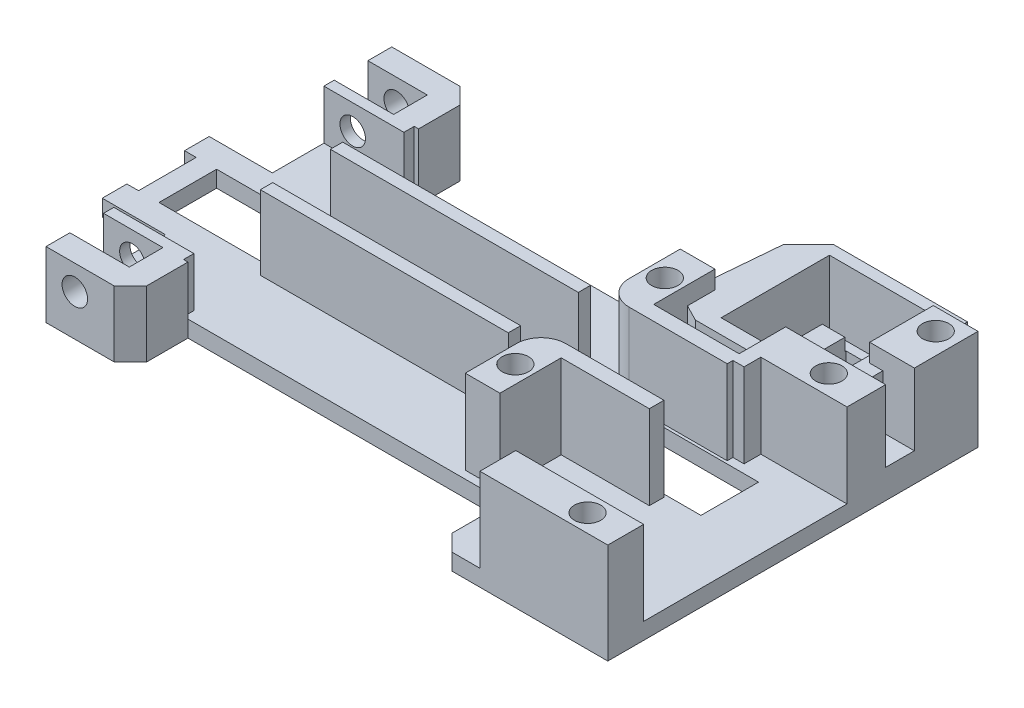
SolidWorks part; units mm, degrees
material "ABS"
ref_plane "前视基准面" through (0, 0, 0) normal (0, 0, 1) x (1, 0, 0)
ref_plane "上视基准面" through (0, 0, 0) normal (0, 1, 0) x (1, 0, 0)
ref_plane "右视基准面" through (0, 0, 0) normal (1, 0, 0) x (0, 0, -1)
sketch "草图1" plane through (0, 0, 0) normal (0, 1, 0) x (1, 0, 0)
  line L0 (-26.5, 14) -> (21.7831, 14)
  line L1 (44.6878, 18.1) -> (44.6878, 3.5) construction
  line L2 (44.6878, 14) -> (44.6878, -14)
  line L3 (44.6878, -18.1) -> (44.6878, -3.5) construction
  line L4 (-26.5, -14) -> (-26.5, -6.4892)
  line L5 (21.7831, -14) -> (-26.5, -14)
  line L6 (23.7831, -16) -> (23.7831, -20.4724)
  line L7 (25.7831, -22.4724) -> (44.6878, -22.4724)
  line L8 (44.6878, -18.1) -> (44.6878, -27.09) construction
  line L9 (49.6864, 0) -> (119.3782, 0) construction
  line L10 (39.6706, 22.4724) -> (44.6878, 22.4724)
  line L11 (23.7831, 16) -> (23.7831, 20.4724)
  line L12 (44.6878, 22.4724) -> (44.6878, 14)
  line L13 (44.6878, -14) -> (44.6878, -22.4724)
  line L14 (37.7008, 24.1809) -> (39.6706, 24.1809)
  line L15 (21.7831, 14) -> (23.7831, 16)
  line L16 (21.7831, -14) -> (23.7831, -16)
  line L17 (23.7831, -20.4724) -> (25.7831, -22.4724)
  line L18 (-32.6682, -6.4892) -> (-26.5, -6.4892)
  line L19 (23.7831, 20.4724) -> (23.7831, 21.4918)
  line L20 (-26.5, -21) -> (-36.5, 21) construction
  line L21 (-32.6682, 4.9064) -> (-32.6682, -4.9064)
  line L22 (-26.5, 21) -> (-36.5, -21) construction
  line L24 (-26.5, 6.4892) -> (-26.5, 14)
  line L25 (23.7831, 21.4918) -> (25.7831, 24.1809)
  line L26 (-32.6682, 3.5) -> (-31.2539, 3.5)
  line L27 (-32.6682, 3.5) -> (-32.6682, -3.5)
  line L28 (-32.6682, -3.5) -> (-31.2539, -3.5)
  line L29 (37.0236, 3.5) -> (37.0236, -3.5)
  line L30 (25.7831, 24.1809) -> (37.7008, 24.1809)
  line L31 (-31.2539, 3.5) -> (-31.2539, -3.5)
  line L32 (39.6706, 24.1809) -> (39.6706, 22.4724)
  line L33 (-32.6682, 4.9064) -> (-32.6682, 6.4892)
  line L34 (-28.7731, -3.5) -> (-28.7731, 3.5)
  line L35 (-32.6682, -4.9064) -> (-32.6682, -6.4892)
  line L36 (-28.7731, 3.5) -> (37.0236, 3.5)
  line L37 (-28.7731, -3.5) -> (37.0236, -3.5)
  line L38 (-32.6682, 6.4892) -> (-26.5, 6.4892)
  point P0 (0, 0)
  point P2 (23.7831, -14)
  point P6 (0, 0)
  point P12 (23.7831, -22.4724)
  point P18 (23.7831, 22.4724)
  point P20 (23.7831, 14)
  dimension "D1" = 7
  dimension "D2" = 28
  dimension "D4" = 2
extrude "凸台-拉伸1" add sketch "草图1" along normal blind 1 contours L4 L0 region at (-2.3584, 0, -13.0966)
extrude "凸台-拉伸4" add sketch "草图1<3>" against normal blind 1 contours L4 L0 region at (-2.3584, 0, -13.0966)
sketch "草图1<3>" plane through (0, 0, 0) normal (0, 1, 0) x (1, 0, 0) same geometry as "草图1"
sketch "草图2" plane through (0, 1, 0) normal (0, 1, 0) x (1, 0, 0)
  line L0 (25.7831, -22.4724) -> (44.6878, -22.4724) construction
  line L1 (29.1607, -22.4724) -> (44.6878, -22.4724)
  line L2 (29.1607, -22.4724) -> (29.1607, -18.118)
  line L3 (29.1607, -18.118) -> (44.6878, -18.118)
  line L4 (44.6878, -22.4724) -> (44.6878, -18.118)
  line L5 (44.6878, 6.5706) -> (34.2253, 6.5706)
  line L6 (44.6878, 22.4724) -> (44.6878, -22.4724) construction
  line L7 (34.2253, 6.5706) -> (34.2253, 4.5345)
  line L8 (34.2253, 4.5345) -> (32.5478, 4.5345)
  line L9 (32.5478, 4.5345) -> (32.5478, 11.2659)
  line L10 (32.5478, 11.2659) -> (44.6878, 11.2659)
  line L11 (22.1731, -9.0716) -> (22.1731, -5.6153)
  line L13 (17.9615, -9.0716) -> (17.9615, -13.0505)
  line L14 (17.9615, -13.0505) -> (22.1731, -13.0505)
  line L15 (22.1731, -9.0716) -> (22.1731, -13.0505)
  line L16 (22.1731, -5.6153) -> (32.8738, -5.6153)
  line L17 (32.8738, -5.6153) -> (32.8738, -3.8374)
  line L18 (32.8738, -3.8374) -> (20.9615, -3.8374)
  line L19 (17.9615, -6.8374) -> (17.9615, -9.0716)
  circle A0 centre (40.0637, 8.9871) radius 1.6
  circle A1 centre (40.0637, -20.3003) radius 1.6
  circle A2 centre (20.0644, -9.0716) radius 1.6
  arc A3 (20.9615, -3.8374) -> (17.9615, -6.8374) centre (20.9615, -6.8374) ccw
  line M9 (25.7831, -22.4724) -> (44.6878, -22.4724)
  line M10 (44.6878, -22.4724) -> (44.6878, 22.4724)
  dimension "D1" = 3.2
  dimension "D2" = 3.2
  dimension "D3" = 3.2
  dimension "D4" = 3
extrude "凸台-拉伸5" add sketch "草图2" along normal blind 10.2 contours L18 A3 L19 L13 L14 L15 L11 L16 L17 A2 | L10 L9 L8 L7 L5 A0 M10 | L3 L2 A1 M9 M10 region at (36.5004, 1, 20.2945) region at (38.0546, 1, -8.6882) region at (21.9978, 1, 11.0611)
sketch "草图3" plane through (0, -1, 0) normal (0, -1, 0) x (1, 0, 0)
  line L0 (9.4165, 0) -> (-12.0062, 0) construction
  line L1 (-26.3758, -14) -> (-15.2845, -14)
  line L2 (-26.3758, -14) -> (-26.3758, -12.7491)
  line L3 (-26.3758, -12.7491) -> (-15.2845, -12.7491)
  line L4 (-15.2845, -14) -> (-15.2845, -12.7491)
  line L5 (-26.3758, 14) -> (-26.3758, 12.7491)
  line L6 (-26.3758, 14) -> (-15.2845, 14)
  line L7 (-15.2845, 14) -> (-15.2845, 12.7491)
  line L8 (-26.3758, 12.7491) -> (-15.2845, 12.7491)
  line L9 (21.7831, 14) -> (-26.5, 14) construction
  dimension "D1" = 0
extrude "凸台-拉伸6" add sketch "草图3" against normal blind 8
sketch "草图4" plane through (0, -1, 0) normal (0, -1, 0) x (1, 0, 0)
  line L0 (-14.7525, -14) -> (-14.7525, -19.024)
  line L1 (-15.2845, -14) -> (21.7831, -14) construction
  line L2 (-14.7525, -19.024) -> (-16.7158, -20.9873)
  line L3 (-16.7158, -20.9873) -> (-26.5, -20.9873)
  line L4 (-26.5, -11) -> (-26.5, -21) construction
  line L5 (-26.5, -20.9873) -> (-26.5, -18.0918)
  line L6 (-26.5, -18.0918) -> (-17.7871, -18.0918)
  line L7 (-17.7871, -18.0918) -> (-17.7871, -14)
  line L8 (-17.7871, -14) -> (-14.7525, -14)
  line L9 (13.3255, 0) -> (-14.7525, 0) construction
  line L10 (-26.5, 20.9873) -> (-26.5, 18.0918)
  line L11 (-16.7158, 20.9873) -> (-26.5, 20.9873)
  line L12 (-26.5, 18.0918) -> (-17.7871, 18.0918)
  line L13 (-17.7871, 18.0918) -> (-17.7871, 14)
  line L14 (-14.7525, 14) -> (-14.7525, 19.024)
  line L15 (-14.7525, 19.024) -> (-16.7158, 20.9873)
  line L16 (-17.7871, 14) -> (-14.7525, 14)
extrude "凸台-拉伸7" add sketch "草图4" against normal blind 8
sketch "草图5" plane through (0, 0, 20.9873) normal (0, 0, 1) x (1, 0, 0)
  circle A0 centre (-21.5, 4) radius 1.55
extrude "切除-拉伸1" cut sketch "草图5" against normal through all
sketch "草图6" plane through (0, 1, 0) normal (0, 1, 0) x (1, 0, 0)
  line L0 (-32.6682, 3.5) -> (-31.2539, 3.5) construction
  line L1 (-14.9638, 3.5) -> (15.1321, 3.5)
  line L2 (-14.9638, 3.5) -> (-14.9638, 5)
  line L3 (-14.9638, 5) -> (15.1321, 5)
  line L4 (15.1321, 3.5) -> (15.1321, 5)
  line L5 (-38.4117, 0) -> (-59.6326, 0) construction
  line L6 (-38.4117, -6.2) -> (-38.4117, 6.2) construction
  line L7 (15.1321, -3.5) -> (15.1321, -5)
  line L8 (-14.9638, -5) -> (15.1321, -5)
  line L9 (-14.9638, -3.5) -> (-14.9638, -5)
  line L10 (-14.9638, -3.5) -> (15.1321, -3.5)
  dimension "D1" = 1.5
extrude "凸台-拉伸8" add sketch "草图6" along normal blind 9
sketch "草图9" plane through (0, 1, 0) normal (0, 1, 0) x (1, 0, 0)
  line L0 (32.8738, -3.8374) -> (20.9615, -3.8374) construction
  line L4 (22.1731, -5.6153) -> (32.8738, -5.6153) construction
  line L6 (17.9615, -13.0505) -> (22.1731, -13.0505) construction
  line L10 (-53.0838, 0) -> (-35.9122, 0) construction
  line L11 (17.9615, 6.8374) -> (17.9615, 13.0505)
  line L12 (17.9615, 13.0505) -> (22.1731, 13.0505)
  line L13 (22.1731, 5.6153) -> (32.8738, 5.6153)
  line L14 (22.1731, 5.6153) -> (22.1731, 13.0505)
  line L15 (32.8738, 3.8374) -> (20.9615, 3.8374)
  line L16 (32.8738, 3.8374) -> (32.8738, 5.6153)
  arc A0 (20.9615, -3.8374) -> (17.9615, -6.8374) centre (20.9615, -6.8374) ccw construction
  circle A1 centre (20.0644, -9.0716) radius 1.6 construction
  arc A2 (20.9615, 3.8374) -> (17.9615, 6.8374) centre (20.9615, 6.8374) cw
  circle A4 centre (20.0644, 9.0716) radius 1.6
extrude "凸台-拉伸9" add sketch "草图9" along normal up to surface (10.2 mm away) up to face at (20.0644, 11.2, 10.6716)
sketch "草图10" plane through (0, 1, 0) normal (0, 1, 0) x (1, 0, 0)
  line L1 (44.6878, 11.2659) -> (25.7831, 11.2659)
  line L2 (44.6878, 11.2659) -> (44.6878, 22.4724)
  line L3 (44.6878, 22.4724) -> (25.7831, 22.4724)
  line L4 (25.7831, 11.2659) -> (25.7831, 22.4724)
extrude "凸台-拉伸10" add sketch "草图10" along normal blind 1.5
sketch "草图11" plane through (0, -1, 0) normal (0, -1, 0) x (1, 0, 0)
  line L0 (32.5478, -10.5053) -> (25.4679, -10.5053)
  line L1 (32.5478, -5.6153) -> (32.5478, -11.2659) construction
  line L2 (25.4679, -10.5053) -> (25.4679, -23.6593)
  line L3 (25.4679, -23.6593) -> (38.4386, -23.6593)
  line L4 (38.4386, -23.6593) -> (38.4386, -11.2659)
  line L5 (32.5478, -11.2659) -> (44.6878, -11.2659) construction
  line L6 (38.4386, -11.2659) -> (40.8637, -11.2659)
  line L7 (40.8637, -11.2659) -> (40.8637, -25.0292)
  line L8 (40.8637, -25.0292) -> (24.6364, -25.0292)
  line L9 (24.6364, -25.0292) -> (21.5472, -21.94)
  line L10 (21.5472, -21.94) -> (20.5509, -10.5637)
  line L12 (32.5478, -10.5053) -> (32.5478, -8.7073)
  line L13 (32.5478, -8.7073) -> (24.1296, -8.7073)
  line L14 (24.1296, -8.7073) -> (20.5509, -10.5637)
extrude "凸台-拉伸11" add sketch "草图11" against normal blind 10
sketch "草图12" plane through (0, -1, 0) normal (0, -1, 0) x (1, 0, 0)
  line L1 (35.155, -22.6004) -> (28.5354, -22.6004)
  line L2 (35.155, -22.6004) -> (35.155, -12.3923)
  line L3 (35.155, -12.3923) -> (28.5354, -12.3923)
  line L4 (28.5354, -22.6004) -> (28.5354, -12.3923)
extrude "切除-拉伸2" cut sketch "草图12" against normal blind 4
sketch "草图13" plane through (0, 2.5, 0) normal (0, 1, 0) x (1, 0, 0)
  line L1 (44.6878, 22.4724) -> (39.2668, 22.4724)
  line L2 (44.6878, 22.4724) -> (44.6878, 14.7489)
  line L3 (44.6878, 14.7489) -> (39.2668, 14.7489)
  line L4 (39.2668, 22.4724) -> (39.2668, 14.7489)
extrude "凸台-拉伸12" add sketch "草图13" along normal up to surface (8.7 mm away) up to face at (29.9445, 11.2, -7.3819)
sketch "草图14" plane through (0, 11.2, 0) normal (0, 1, 0) x (1, 0, 0)
  circle A0 centre (42.105, 19.9215) radius 1.6
  dimension "D1" = 3.2
extrude "切除-拉伸3" cut sketch "草图14" against normal blind 8
sketch "草图15" plane through (0, 7, 0) normal (0, 1, 0) x (1, 0, 0)
  line L0 (-32.6682, 6.4892) -> (-26.5, 6.4892) construction
  line L1 (-26.5, 20.9873) -> (-25, 20.9873)
  line L2 (-26.5, 20.9873) -> (-26.5, 6.4892)
  line L3 (-26.5, 6.4892) -> (-25, 6.4892)
  line L4 (-25, 20.9873) -> (-25, 6.4892)
  line L5 (-41.0064, 0) -> (-53.0838, 0) construction
  line L6 (-46.8944, 0) -> (-20.0243, 0) construction
  line L7 (-25, -20.9873) -> (-25, -6.4892)
  line L8 (-26.5, -6.4892) -> (-25, -6.4892)
  line L9 (-26.5, -20.9873) -> (-26.5, -6.4892)
  line L10 (-26.5, -20.9873) -> (-25, -20.9873)
  dimension "D1" = 1.5
  dimension "D2" = 0
extrude "切除-拉伸4" cut sketch "草图15" against normal through all
